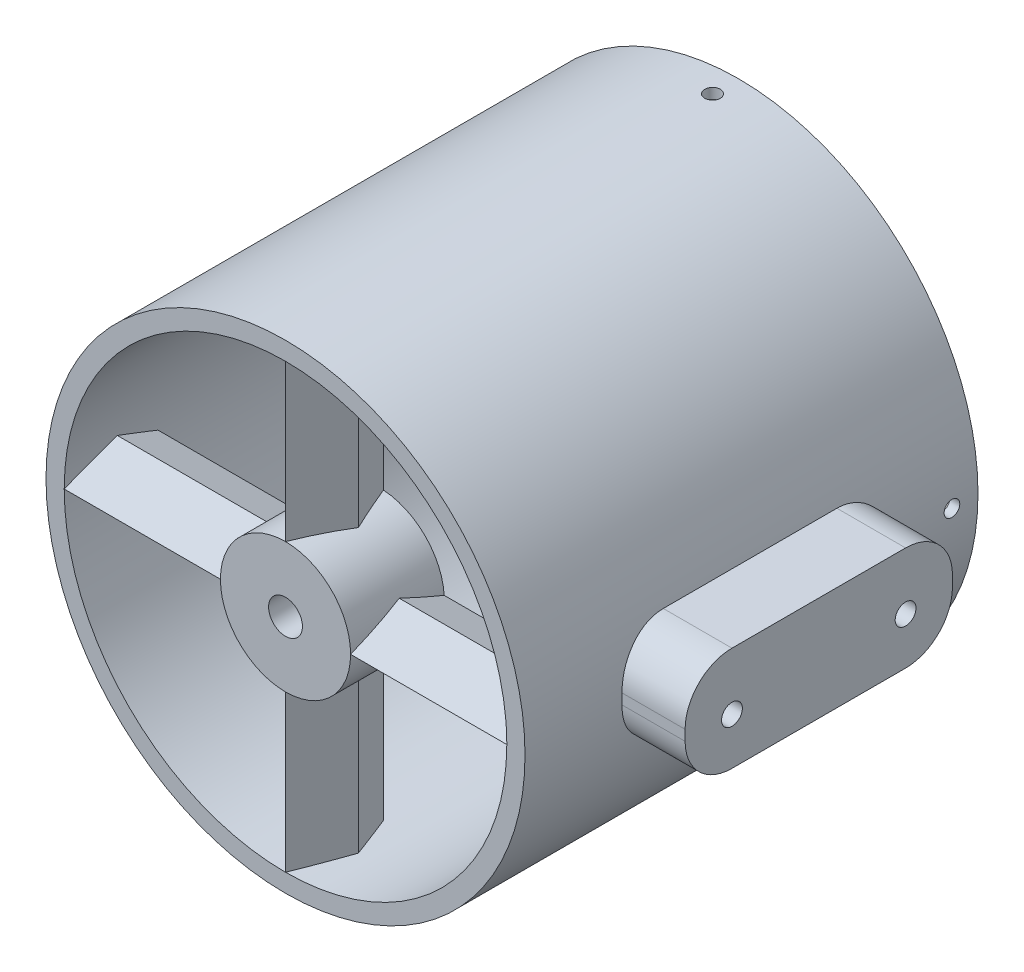
SolidWorks part; units mm, degrees
ref_plane "Ön Düzlem" through (0, 0, 0) normal (0, 0, 1) x (1, 0, 0)
ref_plane "Üst Düzlem" through (0, 0, 0) normal (0, 1, 0) x (1, 0, 0)
ref_plane "Sağ Düzlem" through (0, 0, 0) normal (1, 0, 0) x (0, 0, -1)
sketch "Çizim1" plane through (0, 0, 0) normal (0, 0, 1) x (1, 0, 0)
  circle A0 centre (-2.0933, -2.4974) radius 12.5
  dimension "D1" = 25
extrude "Yükseklik-Ekstrüzyon1" add sketch "Çizim1" along normal blind 20
sketch "Çizim2" plane through (0, 0, 0) normal (1, 0, 0) x (0, 0, -1)
  line L0 (-20, -2.4974) -> (-10, 1.5026)
  line L1 (-20, 10.0026) -> (-20, -14.9974) construction
  line L2 (-10, 1.5026) -> (0, -2.4974)
  line L3 (0, -14.9974) -> (0, 10.0026) construction
  line L4 (0, -2.4974) -> (-10, -6.4974)
  line L5 (-10, -6.4974) -> (-20, -2.4974)
  line L6 (-20, -2.4974) -> (0, -2.4974)
  dimension "D1" = 4
  dimension "D2" = 4
extrude "Yükseklik-Ekstrüzyon3" add sketch "Çizim2" against normal blind 93 and the other way blind 81 contours L0 L6 L2 | L6 L5 L4 region at (0, -3.8307, 10) region at (0, -1.1641, 10)
sketch "Çizim3" plane through (0, 0, 0) normal (0, 1, 0) x (1, 0, 0)
  line L0 (-2.0933, -20) -> (-2.0933, 0)
  line L1 (-14.5933, -20) -> (10.4067, -20) construction
  line L2 (10.4067, 0) -> (-14.5933, 0) construction
  line L3 (-2.0933, 0) -> (1.9067, -10)
  line L4 (1.9067, -10) -> (-2.0933, -20)
  line L5 (-2.0933, -20) -> (-6.0933, -10)
  line L6 (-6.0933, -10) -> (-2.0933, 0)
  dimension "D1" = 4
  dimension "D2" = 4
extrude "Yükseklik-Ekstrüzyon4" add sketch "Çizim3" against normal blind 96 and the other way blind 95 contours L6 L5 L0 | L4 L3 L0 region at (-3.4266, 0, 10) region at (-0.76, 0, 10)
sketch "Çizim4" plane through (0, 0, 0) normal (0, 0, 1) x (1, 0, 0)
  circle A0 centre (-2.0933, -2.4974) radius 42.5
  circle A1 centre (-2.0933, -2.4974) radius 44.5
  dimension "D1" = 85
  dimension "D2" = 89
extrude "Yükseklik-Ekstrüzyon5" add sketch "Çizim4" along normal blind 20 and the other way blind 67
sketch "Çizim5" plane through (0, 0, 0) normal (0, 1, 0) x (1, 0, 0)
  line L0 (-2.0933, 67) -> (-6.0933, 67)
  line L1 (42.4067, 67) -> (-46.5933, 67) construction
  line L2 (-6.0933, 67) -> (-6.0933, 54)
  line L3 (-6.0933, 54) -> (1.9067, 54)
  line L4 (1.9067, 54) -> (1.9067, 67)
  line L5 (1.9067, 67) -> (-2.0933, 67)
  dimension "D1" = 13
  dimension "D2" = 8
  dimension "D3" = 4
extrude "Kes-Ekstrüzyon1" cut sketch "Çizim5" against normal blind 46.5 and the other way blind 41.5 contours L5 L0 L2 L3 L4
ref_plane "Düzlem1" through (-13.936, -6.4974, 10) normal (-0.1245, 0.3685, -0.9213) x (-0.9922, -0.0462, 0.1156)
sketch "Çizim7" plane through (0, 0, 0) normal (0, 0, 1) x (1, 0, 0)
  circle A1 centre (-2.0933, -2.4974) radius 44.5
  circle A3 centre (-2.0933, -2.4974) radius 46
  dimension "D1" = 92
extrude "Yükseklik-Ekstrüzyon10" add sketch "Çizim7" against normal blind 67 and the other way blind 20
sketch "Çizim8" plane through (0, 0, 0) normal (1, 0, 0) x (0, 0, -1)
  line L0 (67, -2.4974) -> (67, 1.5026)
  line L1 (67, -48.4974) -> (67, 43.5026) construction
  line L2 (67, 1.5026) -> (54, 1.5026)
  line L3 (54, 1.5026) -> (54, -6.4974)
  line L4 (54, -6.4974) -> (67, -6.4974)
  line L5 (67, -6.4974) -> (67, -2.4974)
  dimension "D1" = 8
  dimension "D2" = 4
  dimension "D3" = 13
extrude "Kes-Ekstrüzyon2" cut sketch "Çizim8" against normal blind 46 and the other way blind 42
sketch "Çizim9" plane through (0, 0, 0) normal (1, 0, 0) x (0, 0, -1)
  line L0 (67, -2.4974) -> (62, -2.4974)
  line L1 (67, -48.4974) -> (67, 43.5026) construction
  circle A0 centre (62, -2.4974) radius 1.5
  dimension "D2" = 3
  dimension "D1" = 5
extrude "Kes-Ekstrüzyon3" cut sketch "Çizim9" against normal blind 54 and the other way blind 58 contours A0
sketch "Çizim10" plane through (0, 0, 0) normal (0, 1, 0) x (1, 0, 0)
  line L0 (-2.0933, 67) -> (-2.0933, 62)
  line L1 (43.9067, 67) -> (-48.0933, 67) construction
  circle A1 centre (-2.0933, 62) radius 1.5
  dimension "D2" = 3
  dimension "D1" = 5
extrude "Kes-Ekstrüzyon4" cut sketch "Çizim10" against normal blind 59 and the other way blind 60 contours A1
sketch "Çizim11" plane through (0, 0, 0) normal (0, 0, 1) x (1, 0, 0)
  circle A0 centre (-2.0933, -2.4974) radius 46
  circle A1 centre (-2.0933, -2.4974) radius 109.0489
extrude "Kes-Ekstrüzyon5" cut sketch "Çizim11" against normal blind 96 and the other way blind 114
sketch "Çizim12" plane through (0, 0, 0) normal (0, 0, 1) x (1, 0, 0)
  circle A0 centre (-2.0933, -2.4974) radius 3.25
  dimension "D1" = 6.5
extrude "Kes-Ekstrüzyon6" cut sketch "Çizim12" along normal blind 77 and the other way blind 64
sketch "Çizim13" plane through (0, 0, 0) normal (1, 0, 0) x (0, 0, -1)
  line L0 (-20, -2.4974) -> (-20, 7.5026)
  line L1 (-20, 43.5026) -> (-20, -48.4974) construction
  line L3 (50, -1.4974) -> (50, -3.4974)
  line L5 (-20, -12.4974) -> (-20, -2.4974)
  line L6 (-1.3459, -1.4974) -> (-1.3459, -3.4974)
  line L7 (7.6541, 7.5026) -> (41, 7.5026)
  line L8 (7.6541, -12.4974) -> (41, -12.4974)
  arc A0 (7.6541, 7.5026) -> (-1.3459, -1.4974) centre (7.6541, -1.4974) ccw
  arc A1 (50, -1.4974) -> (41, 7.5026) centre (41, -1.4974) ccw
  arc A2 (41, -12.4974) -> (50, -3.4974) centre (41, -3.4974) ccw
  arc A3 (7.6541, -12.4974) -> (-1.3459, -3.4974) centre (7.6541, -3.4974) cw
  circle A4 centre (7.6541, -3.4974) radius 2
  circle A5 centre (41, -3.4974) radius 2
  point P13 (50, 7.5026)
  dimension "D4" = 9
  dimension "D5" = 9
  dimension "D6" = 4
  dimension "D7" = 4
  dimension "D1" = 10
  dimension "D2" = 10
  dimension "D3" = 70
extrude "Yükseklik-Ekstrüzyon12" add sketch "Çizim13" along normal blind 56 contours A3 L8 A2 L3 A1 L7 A0 L6 A5 A4 region at (0, -2.4704, -24.3271)
sketch "Çizim14" plane through (0, 0, 0) normal (0, 0, -1) x (-1, 0, 0)
  circle A1 centre (2.0933, -2.4974) radius 42.5
extrude "Kes-Ekstrüzyon8" cut sketch "Çizim14" along normal blind 75 and the other way blind 2
sketch "Çizim15" plane through (56, 0, 0) normal (1, 0, 0) x (0, 0, -1)
  circle A0 centre (7.6541, -3.4974) radius 2
  circle A1 centre (41, -3.4974) radius 2
extrude "Kes-Ekstrüzyon9" cut sketch "Çizim15" against normal blind 75
